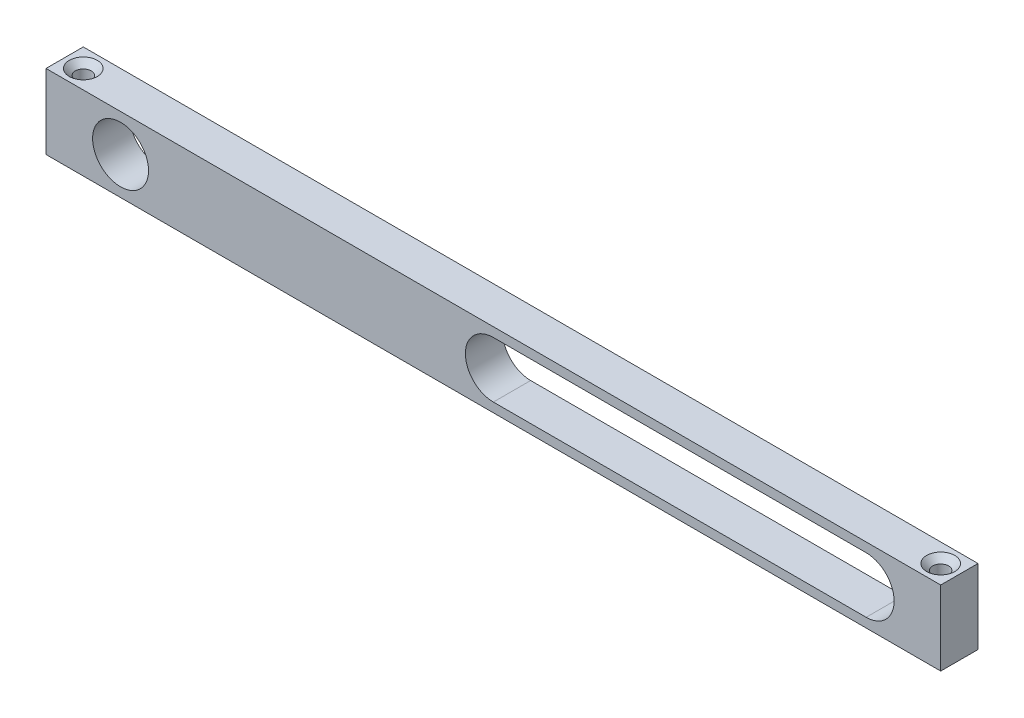
SolidWorks part; units mm, degrees
ref_plane "Front Plane" through (0, 0, 0) normal (0, 0, 1) x (1, 0, 0)
ref_plane "Top Plane" through (0, 0, 0) normal (0, 1, 0) x (1, 0, 0)
ref_plane "Right Plane" through (0, 0, 0) normal (1, 0, 0) x (0, 0, -1)
sketch "Sketch2" plane through (0, 0, 0) normal (0, 0, 1) x (1, 0, 0)
  line L1 (-76.2, -6.35) -> (76.2, -6.35)
  line L2 (-76.2, -6.35) -> (-76.2, 6.35)
  line L3 (-76.2, 6.35) -> (76.2, 6.35)
  line L4 (76.2, -6.35) -> (76.2, 6.35)
  line L5 (-76.2, -6.35) -> (76.2, 6.35) construction
  line L6 (-76.2, 6.35) -> (76.2, -6.35) construction
  line L7 (0, -4.7625) -> (63.5, -4.7625)
  line L9 (0, 4.7625) -> (63.5, 4.7625)
  arc A0 (63.5, -4.7625) -> (63.5, 4.7625) centre (63.5, 0) ccw
  arc A2 (0, 4.7625) -> (0, -4.7625) centre (0, 0) ccw
  circle A3 centre (-63.5, 0) radius 4.7625
  point P0 (0, 0)
  dimension "D3" = 9.525
  dimension "D6" = 9.525
  dimension "D1" = 152.4
  dimension "D2" = 12.7
  dimension "D4" = 6.35
  dimension "D5" = 63.5
  dimension "D7" = 63.5
  dimension "D8" = 6.35
extrude "Boss-Extrude1" add sketch "Sketch2" along normal blind 6.35
hole_wizard "#6-32 Tapped Hole1" positions "Sketch5" profile "Sketch4" tap size "#6-32" standard "ANSI Inch" end condition through all
sketch "Sketch5" plane through (0, 6.35, 0) normal (0, 1, 0) x (1, 0, 0)
  line L0 (76.2, 0) -> (-76.2, 0) construction
  line L1 (-76.2, -6.35) -> (-76.2, 0) construction
  point P0 (-73.025, -3.175)
  dimension "D1" = 3.175
  dimension "D2" = 3.175
sketch "Sketch4" plane through (-73.025, 6.35, 3.175) normal (1, 0, 0) x (0, 0, 1)
  line L0 (0, 0) -> (0, 12.7)
  line L1 (0, 12.7) -> (1.3525, 12.7)
  line L2 (1.3525, 12.7) -> (1.3525, 1.0351)
  line L3 (1.3525, 1.0351) -> (2.3876, 0)
  line L5 (2.3876, 0) -> (0, 0)
  line L6 (-1.3525, 1.0351) -> (-2.3876, 0) construction
  line L11 (0, -6.35) -> (0, 107.95) construction
  dimension "Thru Tap Drill Dia." = 2.7051
  dimension "Thru Tap Drill Depth" = 12.7
  dimension "Near C'Sink Dia." = 4.7752
  dimension "Near C'Sink Angle" = 90
cosmetic thread "Hole Thread1"
hole_wizard "#6-32 Tapped Hole2" positions "Sketch6" profile "Sketch7" tap size "#6-32" standard "ANSI Inch" end condition through all
sketch "Sketch6" plane through (0, 6.35, 0) normal (0, 1, 0) x (1, 0, 0)
  line L0 (76.2, 0) -> (-76.2, 0) construction
  line L1 (76.2, -6.35) -> (76.2, 0) construction
  point P0 (73.025, -3.175)
  dimension "D1" = 3.175
  dimension "D2" = 3.175
sketch "Sketch7" plane through (73.025, 6.35, 3.175) normal (1, 0, 0) x (0, 0, 1)
  line L0 (0, 0) -> (0, 12.7)
  line L1 (0, 12.7) -> (1.3525, 12.7)
  line L2 (1.3525, 12.7) -> (1.3525, 1.035)
  line L3 (1.3525, 1.035) -> (2.3876, 0)
  line L5 (2.3876, 0) -> (0, 0)
  line L6 (-1.3525, 1.035) -> (-2.3876, 0) construction
  line L11 (0, -6.35) -> (0, 107.95) construction
  dimension "Thru Tap Drill Dia." = 2.7051
  dimension "Thru Tap Drill Depth" = 12.7
  dimension "Near C'Sink Dia." = 4.7752
  dimension "Near C'Sink Angle" = 90
cosmetic thread "Hole Thread2"
